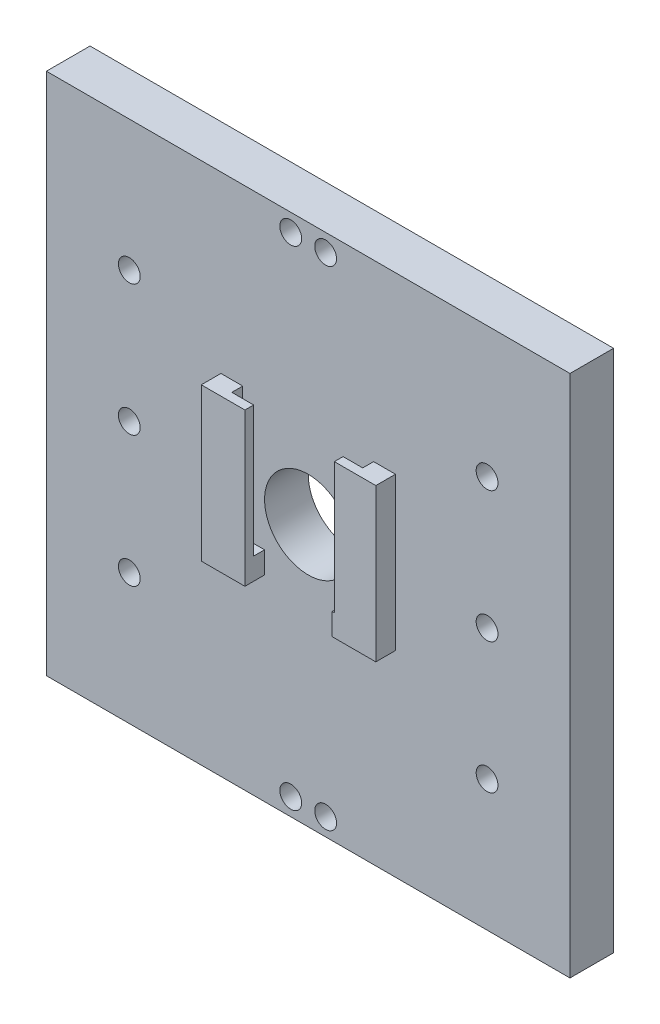
SolidWorks part; units mm, degrees
ref_plane "Front Plane" through (0, 0, 0) normal (0, 0, 1) x (1, 0, 0)
ref_plane "Top Plane" through (0, 0, 0) normal (0, 1, 0) x (1, 0, 0)
ref_plane "Right Plane" through (0, 0, 0) normal (1, 0, 0) x (0, 0, -1)
sketch "Sketch1" plane through (0, 0, 0) normal (0, 1, 0) x (1, 0, 0)
  line L1 (-60, -5) -> (60, -5)
  line L2 (-60, -5) -> (-60, 5)
  line L3 (-60, 5) -> (60, 5)
  line L4 (60, -5) -> (60, 5)
  line L5 (-60, -5) -> (60, 5) construction
  line L6 (-60, 5) -> (60, -5) construction
  point P0 (0, 0)
  dimension "D1" = 120
  dimension "D2" = 10
extrude "Boss-Extrude1" add sketch "Sketch1" along normal blind 120
sketch "Sketch2" plane through (0, 0, 5) normal (0, 0, 1) x (1, 0, 0)
  line L0 (60, 120) -> (-60, 120) construction
  line L1 (60, 0) -> (-60, 0) construction
  line L2 (-15, 50) -> (-15, 75)
  line L4 (-20, 75) -> (-20, 45)
  line L5 (-20, 45) -> (-15, 45)
  line L6 (60, 120) -> (60, 0) construction
  line L11 (15, 50) -> (15, 75)
  line L13 (20, 75) -> (20, 45)
  line L14 (20, 45) -> (15, 45)
  line L16 (-15, 50) -> (-10, 50)
  line L17 (-10, 50) -> (-10, 45)
  line L18 (-10, 45) -> (-15, 45)
  line L19 (15, 45) -> (10, 45)
  line L20 (10, 45) -> (10, 50)
  line L21 (10, 50) -> (15, 50)
  line L22 (15, 75) -> (15, 80)
  line L23 (15, 80) -> (20, 80)
  line L24 (20, 80) -> (20, 75)
  line L25 (-15, 75) -> (-15, 80)
  line L26 (-15, 80) -> (-20, 80)
  line L27 (-20, 80) -> (-20, 75)
  circle A0 centre (0, 60) radius 10
  circle A1 centre (-41, 60) radius 2.5
  circle A2 centre (-41, 30) radius 2.5
  circle A3 centre (-41, 90) radius 2.5
  circle A4 centre (41, 60) radius 2.5
  circle A5 centre (41, 30) radius 2.5
  circle A6 centre (41, 90) radius 2.5
  circle A7 centre (-4, 116) radius 2.5
  circle A8 centre (4, 116) radius 2.5
  circle A9 centre (-4, 4) radius 2.5
  circle A10 centre (4, 4) radius 2.5
  point P0 (0, 0)
  point P1 (0, 60)
  dimension "D3" = 41
  dimension "D4" = 30
  dimension "D9" = 4
  dimension "D14" = 4
  dimension "D15" = 8
  dimension "D16" = 20
  dimension "D1" = 60
  dimension "D2" = 60
  dimension "D5" = 30
  dimension "D6" = 41
  dimension "D7" = 30
  dimension "D8" = 30
  dimension "D10" = 4
  dimension "D11" = 4
  dimension "D12" = 0
  dimension "D13" = 0
  dimension "D18" = 15
  dimension "D19" = 60
  dimension "D20" = 15
extrude "Cut-Extrude1" cut sketch "Sketch2" against normal blind 10 contours A0 | A3 | A1 | A2 | A5 | A4 | A7 | A8 | A6 | A9 | A10
extrude "Boss-Extrude2" add sketch "Sketch2<4>" along normal blind 4.5 contours L14 L13 L11 | L4 L5 L18 L17 L16 L2 L25 L26 L27 region at (16.875, 60.625, 5)
sketch "Sketch2<4>" plane through (0, 0, 5) normal (0, 0, 1) x (1, 0, 0) same geometry as "Sketch2"
sketch "Sketch3" plane through (-15, 0, 0) normal (1, 0, 0) x (0, 0, -1)
  line L6 (-9.5, 50) -> (-9.5, 80)
  line L7 (-9.5, 80) -> (-7.5, 80)
  line L8 (-9.5, 80) -> (-5, 80) construction
  line L9 (-7.5, 80) -> (-7.5, 50)
  line L10 (-9.5, 50) -> (-5, 50) construction
  line L11 (-7.5, 50) -> (-9.5, 50)
extrude "Boss-Extrude4" add sketch "Sketch3" along normal blind 5
sketch "Sketch5" plane through (15, 0, 0) normal (-1, 0, 0) x (0, 0, 1)
  line L1 (9.5, 80) -> (9.5, 50)
  line L3 (9.5, 50) -> (7.5, 50)
  line L6 (9.5, 80) -> (7.5, 80)
  line L7 (9.5, 80) -> (5, 80) construction
  line L8 (9.5, 50) -> (5, 50) construction
  line L9 (7.5, 50) -> (7.5, 80)
extrude "Boss-Extrude5" add sketch "Sketch5" along normal blind 4.5
